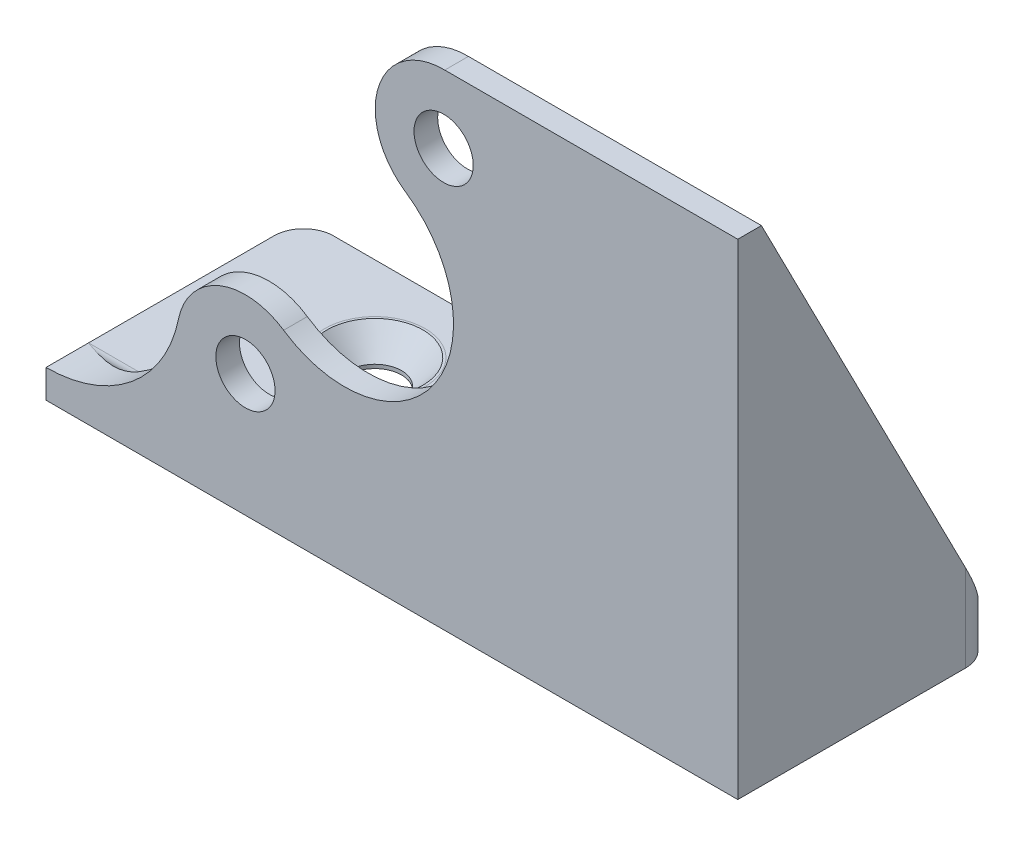
SolidWorks part; units mm, degrees
material "UNS A97075 7075-T651 2.501–3.000 in plate (F_ty = 56 ksi)"
ref_plane "Front Plane" through (0, 0, 0) normal (0, 0, 1) x (1, 0, 0)
ref_plane "Top Plane" through (0, 0, 0) normal (0, 1, 0) x (1, 0, 0)
ref_plane "Right Plane" through (0, 0, 0) normal (1, 0, 0) x (0, 0, -1)
sketch "Sketch2" plane through (0, 0, 0) normal (0, 0, 1) x (1, 0, 0)
  line L1 (0, 0) -> (101.6, 0)
  line L2 (0, 0) -> (0, 127)
  line L3 (0, 127) -> (101.6, 127)
  line L4 (101.6, 0) -> (101.6, 127)
  dimension "D1" = 101.6
  dimension "D2" = 127
extrude "Boss-Extrude1" add sketch "Sketch2" along normal blind 3.175
sketch "Sketch3" [suppressed] plane through (0, 0, 3.175) normal (0, 0, 1) x (1, 0, 0)
  line L0 (101.6, 0) -> (101.6, 127) construction
  line L1 (0, 0) -> (101.6, 0)
  line L2 (0, 0) -> (0, 12.1088)
  line L3 (0, 12.1088) -> (101.6, 12.1088)
  line L4 (101.6, 0) -> (101.6, 12.1088)
extrude "Boss-Extrude2" [suppressed] add sketch "Sketch3" along normal blind 25.4
sketch "Sketch5" plane through (0, 0, 0) normal (0, 0, -1) x (-1, 0, 0)
  line L0 (-58.5712, 65.1526) -> (-81.5862, 65.1526)
  line L1 (-81.5862, 0) -> (-97.9068, 0)
  line L2 (-81.5862, 0) -> (-5.0343, 0)
  line L3 (-5.0343, 0) -> (-5.0343, 3.81)
  line L4 (0, 0) -> (-101.6, 0) construction
  line L5 (-81.5862, 0) -> (-81.5862, 65.1526) construction
  line L6 (-97.9068, 0) -> (-97.9068, 65.1526)
  line L7 (-97.9068, 65.1526) -> (-81.5862, 65.1526)
  line L8 (0, 127) -> (0, 0) construction
  line L9 (-4.9708, 0.0028) -> (-4.9708, -2.9972) construction
  line L10 (-101.6, 0) -> (-101.6, 127) construction
  line L11 (-97.9708, -2.9972) -> (-97.9708, 0.0028) construction
  circle A12 centre (-58.4162, 55.9739) radius 3.9751
  arc A13 (-53.2878, 48.36) -> (-58.5712, 65.1526) centre (-58.4162, 55.9739) ccw
  arc A14 (-53.2878, 48.36) -> (-36.9387, 24.0877) centre (-45.1132, 36.2238) ccw
  arc A15 (-22.8172, 18.3173) -> (-36.9387, 24.0877) centre (-31.8102, 16.4738) ccw
  circle A16 centre (-31.8102, 16.4738) radius 3.9751
  arc A17 (-5.0343, 3.81) -> (-22.8172, 18.3173) centre (-5.0343, 21.9627) cw
  line M8 (0, 0) -> (0, 127)
  line M9 (0, 127) -> (-101.6, 127)
  line M10 (-101.6, 127) -> (-101.6, 0)
  line M11 (-101.6, 0) -> (0, 0)
  dimension "D1" = 3.81
  dimension "D2" = 76.5519
  dimension "D3" = 92.8726
  dimension "D5" = 5.0343
  dimension "D6" = 0.0635
  dimension "D7" = 3.6932
  dimension "D8" = 0.0639
extrude "Cut-Extrude1" cut sketch "Sketch5" against normal blind 3.175 contours A17 L3 L6 L7 L0 A13 A14 A15 M11 M8 M9 M10 | A12 | A16 region at (44.5357, 77.786, 0) region at (58.4162, 55.9739, 0) region at (31.8102, 16.4738, 0)
sketch "Sketch10" plane through (5.0343, 0, 0) normal (1, 0, 0) x (0, 0, -1)
  line L0 (-3.175, 0) -> (-4.2418, 0)
  line L1 (-4.2418, 0) -> (-4.2418, -2.9972)
  line L2 (-4.2418, -2.9972) -> (-34.5948, -2.9972)
  line L3 (-34.5948, -2.9972) -> (-34.5948, 0)
  line L4 (-34.5948, 0) -> (-4.2418, 0) construction
  line L7 (-3.175, 3.81) -> (-34.5948, 3.81)
  line L8 (-3.175, 3.81) -> (-3.175, 0)
  line L9 (-34.5948, 3.81) -> (-34.5948, 0)
  dimension "D1" = 1.0668
  dimension "D2" = 2.9972
  dimension "D3" = 30.353
  dimension "D4" = 3.81
extrude "Boss-Extrude3" add sketch "Sketch10" along normal up to surface (92.8726 mm away) up to face at (97.9068, 32.5763, 1.5875)
sketch "Sketch11" plane through (97.9068, 0, 0) normal (1, 0, 0) x (0, 0, -1)
  line L1 (-3.175, 3.81) -> (-34.5948, 3.81) construction
  line L3 (-3.175, 65.1526) -> (-3.175, 3.81)
  line L6 (-34.5948, 3.81) -> (-3.175, 3.81)
  line L8 (-34.5948, 3.81) -> (-3.175, 3.81) construction
  line L9 (-34.5948, 3.81) -> (-3.175, 65.1526)
extrude "Boss-Extrude4" add sketch "Sketch11" against normal blind 6.35
sketch "Sketch18" plane through (0, -2.9972, 0) normal (0, -1, 0) x (1, 0, 0)
  circle A2 centre (25.968, 23.2283) radius 3.175
  circle A4 centre (81.868, 23.2283) radius 3.175
extrude "Cut-Extrude3" cut sketch "Sketch18" against normal up to surface (6.8072 mm away) up to face at (48.2956, 3.81, 18.8849)
fillet "Fillet4" radius 4.0005 4 edges at (5.0343, -1.4986, 4.2418) (5.0343, 0.4064, 34.5948) (97.9068, 0.4064, 34.5948) (97.9068, -1.4986, 4.2418) tangent propagation no
sketch "Sketch19" plane through (0, 0, 34.5948) normal (0, 0, 1) x (1, 0, 0)
  line L0 (9.0348, 0.0028) -> (93.9063, 0.0028)
  line L1 (9.0348, 3.81) -> (9.0348, -2.9972) construction
  line L2 (93.9063, -2.9972) -> (93.9063, 3.81) construction
  line L3 (93.9063, -2.9972) -> (9.0348, -2.9972) construction
  dimension "D1" = 3
sketch "Sketch20" plane through (97.9068, 0, 0) normal (1, 0, 0) x (0, 0, -1)
  line L0 (-8.2423, 0) -> (-30.7225, 0)
sketch "Sketch22" plane through (5.0343, 0, 0) normal (-1, 0, 0) x (0, 0, 1)
  line L0 (8.2423, 0) -> (30.5943, 0)
  line L1 (30.5943, -2.9972) -> (30.5943, 3.81) construction
fillet "Fillet5" [suppressed] radius 6.35 tangent propagation no
split line "Split Line1"
split line "Split Line4"
split line "Split Line5"
fillet "Fillet6" [suppressed] radius 6.35
mirror "Mirror5" about plane through (0, 0, 0) normal (0, 0, 1) of bodies 114
sketch "FEA Force Line" plane through (0, 0, -3.175) normal (0, 0, -1) x (-1, 0, 0)
  line L0 (-58.4162, 55.9739) -> (-31.8102, 16.4738)
  line L1 (-45.1132, 36.2238) -> (-57.2494, 28.0493)
  circle A0 centre (-58.4162, 55.9739) radius 3.9751 construction
  circle A2 centre (-31.8102, 16.4738) radius 3.9751 construction
  arc A3 (-53.2878, 48.36) -> (-36.9387, 24.0877) centre (-45.1132, 36.2238) ccw construction
  point P2 (0, 0)
  point P7 (-57.2494, 28.0493)
  point P9 (0, 0)
  point P12 (0, 0)
ref_plane "Plane1" through (14.2491, -9.5978, 0) normal (0.8294, -0.5587, 0) x (-0.5587, -0.8294, 0)
ref_plane "Plane2" through (30.8641, 45.8216, 0) normal (0.5587, 0.8294, 0) x (0.8294, -0.5587, 0)
sketch "Sketch25" plane through (0, 0, 0) normal (0, 0, 1) x (1, 0, 0)
  line L0 (105.4755, -15.2416) -> (106.8408, 71.8338)
  line L1 (105.4755, -15.2416) -> (-9.9073, -13.4325)
  line L2 (106.8408, 71.8338) -> (-8.542, 73.6429)
  line L3 (-9.9073, -13.4325) -> (-8.542, 73.6429)
extrude "Cut-Extrude4" cut sketch "Sketch25" along normal up to surface (34.5948 mm away) up to face at (51.4706, -1.4972, 34.5948)
sketch "Sketch28" plane through (0, -2.9972, 0) normal (0, -1, 0) x (1, 0, 0)
  line L4 (5.0343, -8.2423) -> (5.0343, -30.5943)
  line L6 (9.0348, -34.5948) -> (93.9063, -34.5948)
  line L7 (93.9063, -4.2418) -> (9.0348, -4.2418)
  line L11 (93.9063, -4.2418) -> (9.0348, -4.2418)
  line L13 (97.9068, -30.5943) -> (97.9068, -8.2423)
  line L15 (9.0348, -34.5948) -> (93.9063, -34.5948)
  line L16 (5.0343, -8.2423) -> (5.0343, -30.5943)
  line L17 (97.9068, -30.5943) -> (97.9068, -8.2423)
  arc A5 (5.0343, -30.5943) -> (9.0348, -34.5948) centre (9.0348, -30.5943) ccw
  arc A6 (5.0343, -30.5943) -> (9.0348, -34.5948) centre (9.0348, -30.5943) ccw
  arc A7 (93.9063, -34.5948) -> (97.9068, -30.5943) centre (93.9063, -30.5943) ccw
  arc A12 (93.9063, -34.5948) -> (97.9068, -30.5943) centre (93.9063, -30.5943) ccw
  arc A13 (97.9068, -8.2423) -> (93.9063, -4.2418) centre (93.9063, -8.2423) ccw
  arc A14 (97.9068, -8.2423) -> (93.9063, -4.2418) centre (93.9063, -8.2423) ccw
  arc A15 (9.0348, -4.2418) -> (5.0343, -8.2423) centre (9.0348, -8.2423) ccw
  arc A16 (9.0348, -4.2418) -> (5.0343, -8.2423) centre (9.0348, -8.2423) ccw
  dimension "D1" = 0
extrude "Cut-Extrude5" cut sketch "Sketch28" against normal up to surface (2.9972 mm away) up to face at (51.4706, 0, -3.8852)
sketch "Sketch31" plane through (0, 3.81, 0) normal (0, 1, 0) x (1, 0, 0)
  line L4 (91.5568, 34.5948) -> (9.0348, 34.5948)
  line L6 (5.0343, 30.5943) -> (5.0343, 3.175)
  line L12 (5.0343, 30.5943) -> (5.0343, 3.175)
  line L14 (5.0343, 3.175) -> (91.5568, 3.175)
  line L16 (91.5568, 34.5948) -> (9.0348, 34.5948)
  line L22 (5.0343, 3.175) -> (91.5568, 3.175)
  line L24 (91.5568, 3.175) -> (91.5568, 34.5948)
  line L25 (91.5568, 3.175) -> (91.5568, 34.5948)
  circle A0 centre (81.868, 23.2283) radius 3.175 construction
  arc A1 (9.0348, 34.5948) -> (5.0343, 30.5943) centre (9.0348, 30.5943) ccw
  arc A3 (9.0348, 34.5948) -> (5.0343, 30.5943) centre (9.0348, 30.5943) ccw
  circle A4 centre (25.968, 23.2283) radius 3.175 construction
  circle A5 centre (81.868, 23.2283) radius 3.175
  circle A6 centre (25.968, 23.2283) radius 3.175
  dimension "D1" = 0
fillet "Fillet7" radius 2.54 3 edges at (91.5568, 3.81, -18.8849) (48.2956, 3.81, -3.175) (91.5568, 34.4813, -3.175)
sketch "Sketch33" plane through (0, 3.81, 0) normal (0, 1, 0) x (1, 0, 0)
  circle A0 centre (25.968, 23.2283) radius 6.7437
  circle A1 centre (81.868, 23.2283) radius 6.7437
  dimension "D1" = 13.4874
split line "Split Line6"
hole_wizard "CSK for 1/4 Flat Head Machine Screw (100)1" positions "Sketch34" profile "Sketch35" countersink size "1/4" standard "ANSI Inch" end condition through all
sketch "Sketch34" plane through (0, 3.81, 0) normal (0, 1, 0) x (1, 0, 0)
  point P0 (25.968, 23.2283)
  point P3 (25.968, 23.2283)
  point P7 (81.868, 23.2283)
sketch "Sketch35" plane through (25.968, 3.81, -23.2283) normal (1, 0, 0) x (0, 0, 1)
  line L0 (0, 0) -> (0, 3.81)
  line L1 (0, 3.81) -> (3.5712, 3.81)
  line L2 (3.5712, 3.81) -> (3.5712, 3.2989)
  line L3 (3.5712, 3.2989) -> (6.4389, 0)
  line L5 (6.4389, 0) -> (0, 0)
  line L6 (-3.5712, 3.2989) -> (-6.4389, 0) construction
  line L11 (0, -6.35) -> (0, 107.95) construction
  dimension "Thru Hole Dia." = 7.1425
  dimension "Thru Hole Depth" = 3.81
  dimension "Near C'Sink Dia." = 12.8778
  dimension "Near C'Sink Angle" = 82
